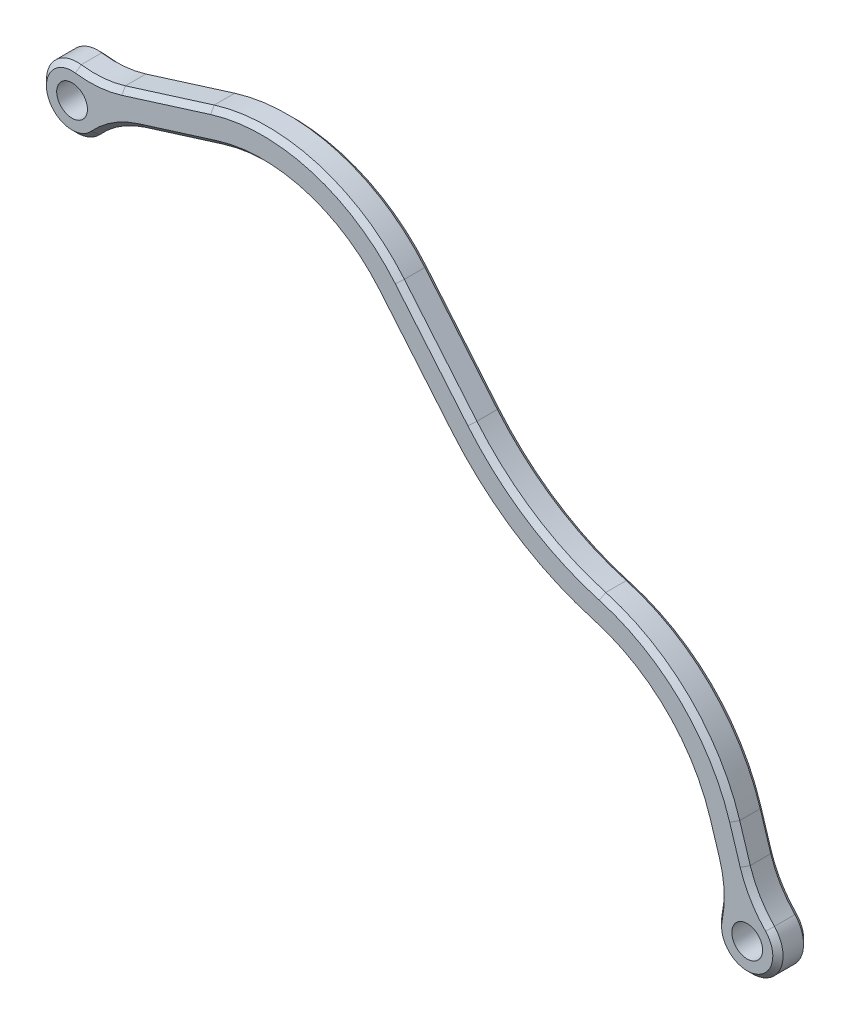
SolidWorks part; units mm, degrees
ref_plane "Спереди" through (0, 0, 0) normal (0, 0, 1) x (1, 0, 0)
ref_plane "Сверху" through (0, 0, 0) normal (0, 1, 0) x (1, 0, 0)
ref_plane "Справа" through (0, 0, 0) normal (1, 0, 0) x (0, 0, -1)
other "Configuration Table"
sketch "Sketch1" plane through (0, 0, 0) normal (0, 0, 1) x (1, 0, 0)
  line L0 (29.1816, 59.1403) -> (31.7687, 57.6215) construction
  line L1 (53.215, 74.5385) -> (56.215, 74.5385) construction
  line L2 (104.6888, 171.3229) -> (107.6888, 171.3229) construction
  line L3 (157.7714, 180.1435) -> (175.4301, 182.1306)
  line L4 (143.4427, 187.7367) -> (195.252, 191.8347)
  line L5 (137.6846, 182.6036) -> (146.4765, 180.7095)
  line L6 (189.1207, 177.3366) -> (200.7976, 165.6524)
  line L7 (138.3165, 185.5363) -> (147.1083, 183.6422)
  line L8 (157.436, 183.1246) -> (175.0946, 185.1118)
  line L9 (191.2427, 179.4573) -> (201.4921, 169.2014)
  line L10 (191.2427, 179.4573) -> (202.9196, 167.7731) construction
  line L11 (157.436, 183.1246) -> (157.7714, 180.1435) construction
  line L12 (175.0946, 185.1118) -> (175.4301, 182.1306) construction
  line L13 (157.436, 183.1246) -> (157.3241, 184.1184)
  line L14 (157.3241, 184.1184) -> (174.9828, 186.1055)
  line L15 (174.9828, 186.1055) -> (175.0946, 185.1118)
  line L16 (175.4301, 182.1306) -> (175.542, 181.1369)
  line L17 (175.542, 181.1369) -> (157.8833, 179.1497)
  line L18 (157.8833, 179.1497) -> (157.7714, 180.1435)
  line L19 (159.3116, 184.342) -> (159.8707, 179.3734)
  line L20 (172.9954, 185.8819) -> (173.5545, 180.9133)
  line L21 (202.3772, 166.3349) -> (201.4921, 157.6593) construction
  line L22 (56.6523, 75.5626) -> (68.509, 79.27)
  line L23 (85.4726, 74.2877) -> (92.5455, 65.8289)
  line L24 (117.9169, 45.4274) -> (120.0668, 38.5517)
  circle A0 centre (120.5779, 36.531) radius 1.5 construction
  circle A1 centre (120.5779, 36.531) radius 3 construction
  circle A2 centre (54.6883, 74.6507) radius 1.5 construction
  arc A4 (112.462, 175.6034) -> (137.6846, 182.6036) centre (131.7487, 155.0512) cw
  circle A5 centre (106.3428, 171.2196) radius 1.5119
  circle A10 centre (106.3428, 171.2196) radius 3
  arc A11 (112.462, 175.6034) -> (109.2166, 170.3586) centre (120.5779, 166.955) ccw
  arc A12 (175.4301, 182.1306) -> (189.1207, 177.3366) centre (177.2991, 165.5224) cw
  circle A13 centre (202.3772, 166.3349) radius 1.5
  circle A14 centre (201.5653, 158.3763) radius 1.5
  arc A15 (199.4019, 165.9506) -> (198.4447, 158.5976) centre (184.9864, 164.0883) cw
  circle A16 centre (201.5653, 158.3763) radius 3
  circle A17 centre (202.3772, 166.3349) radius 3
  arc A18 (205.2135, 165.3577) -> (204.5405, 158.7606) centre (218.9561, 160.6229) ccw
  arc A19 (146.4765, 180.7095) -> (157.7714, 180.1435) centre (153.8542, 214.9537) ccw
  circle A20 centre (92.7693, 185.5363) radius 16.953
  arc A21 (104.9318, 173.867) -> (110.4091, 177.791) centre (92.8918, 196.4576) ccw
  arc A22 (110.4091, 177.791) -> (138.3165, 185.5363) centre (131.7487, 155.0512) cw
  arc A23 (147.1083, 183.6422) -> (157.436, 183.1246) centre (153.8542, 214.9537) ccw
  arc A24 (175.0946, 185.1118) -> (191.2427, 179.4573) centre (177.2991, 165.5224) cw
  arc A25 (110.4091, 177.791) -> (106.3428, 171.2196) centre (120.5779, 166.955) ccw construction
  arc A26 (175.0946, 185.1118) -> (191.2427, 179.4573) centre (177.2991, 165.5224) cw construction
  circle A27 centre (54.6883, 74.6507) radius 3 construction
  arc A28 (68.509, 79.27) -> (85.4726, 74.2877) centre (73.2599, 64.0761) cw
  arc A29 (92.5455, 65.8289) -> (105.8688, 57.1745) centre (113.2794, 83.1656) ccw
  arc A30 (105.8688, 57.1745) -> (117.9169, 45.4274) centre (101.0124, 40.1417) cw
  point P77 (120.0668, 38.5517)
  point P78 (56.5701, 75.751)
  point P79 (56.6523, 75.5626)
  dimension "D2" = 3
  dimension "D3" = 3
  dimension "D4" = 3
  dimension "D5" = 6
  dimension "D6" = 6
  dimension "D7" = 6
  dimension "D8" = 3
  dimension "D9" = 1
  dimension "D15" = 3
  dimension "D16" = 6
  dimension "D17" = 3
  dimension "D18" = 6
  dimension "D10" = 1
  dimension "D11" = 2
  dimension "D12" = 2
  dimension "D13" = 8
  dimension "D14" = 3
extrude "Extrude-Thin1" add sketch "Sketch1" along normal blind 3 thin contours L22 A28 L23 A29 A30 L24 thin type mid plane wall 3
sketch "Sketch2" plane through (0, 0, 0) normal (0, 0, 1) x (1, 0, 0)
  circle A0 centre (54.6883, 74.6507) radius 3
  circle A1 centre (54.6883, 74.6507) radius 1.5
  circle A2 centre (120.5779, 36.531) radius 3
  circle A3 centre (120.5779, 36.531) radius 1.5
  dimension "D1" = 3
  dimension "D2" = 6
  dimension "D3" = 3
extrude "Boss-Extrude1" add sketch "Sketch2" along normal blind 3
fillet "Fillet1" radius 10 4 edges at (118.462, 38.6578, 1.5) (121.3651, 39.4259, 1.5) (57.6688, 74.3088, 1.5) (56.4577, 77.0734, 1.5)
chamfer "Chamfer1" distance 0.5 angle 45 36 edges at (112.3298, 51.7491, 0) (97.7397, 59.2427, 0) (116.9342, 43.5437, 0) (87.8583, 69.0961, 0) (117.8259, 39.6346, 0) (77.3233, 77.9111, 0) (121.4186, 33.6512, 0) (65.1407, 76.6452, 0) (121.3235, 40.4632, 0) (58.9287, 74.3369, 0) (119.8628, 44.2302, 0) (51.8703, 73.6216, 0) (114.4241, 53.8971, 0) (57.2605, 77.5723, 0) (99.3739, 61.7585, 0) (63.7281, 79.3468, 0) (90.1598, 71.0205, 0) (78.1687, 80.7895, 0) (112.3298, 51.7491, 3) (97.7397, 59.2427, 3) (116.9342, 43.5437, 3) (87.8583, 69.0961, 3) (117.8259, 39.6346, 3) (77.3233, 77.9111, 3) (121.4186, 33.6512, 3) (65.1407, 76.6452, 3) (121.3235, 40.4632, 3) (58.9287, 74.3369, 3) (119.8628, 44.2302, 3) (51.8703, 73.6216, 3) (114.4241, 53.8971, 3) (57.2605, 77.5723, 3) (99.3739, 61.7585, 3) (63.7281, 79.3468, 3) (90.1598, 71.0205, 3) (78.1687, 80.7895, 3)
